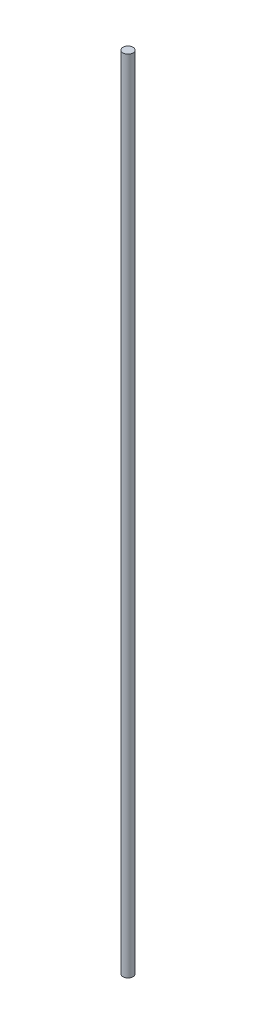
SolidWorks part; units mm, degrees
material "AISI 1020"
ref_plane "Front Plane" through (0, 0, 0) normal (0, 0, 1) x (1, 0, 0)
ref_plane "Top Plane" through (0, 0, 0) normal (0, 1, 0) x (1, 0, 0)
ref_plane "Right Plane" through (0, 0, 0) normal (1, 0, 0) x (0, 0, -1)
sketch "Sketch1" plane through (0, 0, 0) normal (0, 1, 0) x (1, 0, 0)
  circle A0 centre (0, 0) radius 2
  dimension "D1" = 4
extrude "Boss-Extrude2" add sketch "Sketch1" along normal blind 160 and the other way blind 160
cosmetic thread "Cosmetic Thread1" parameters "D2"=3.22
